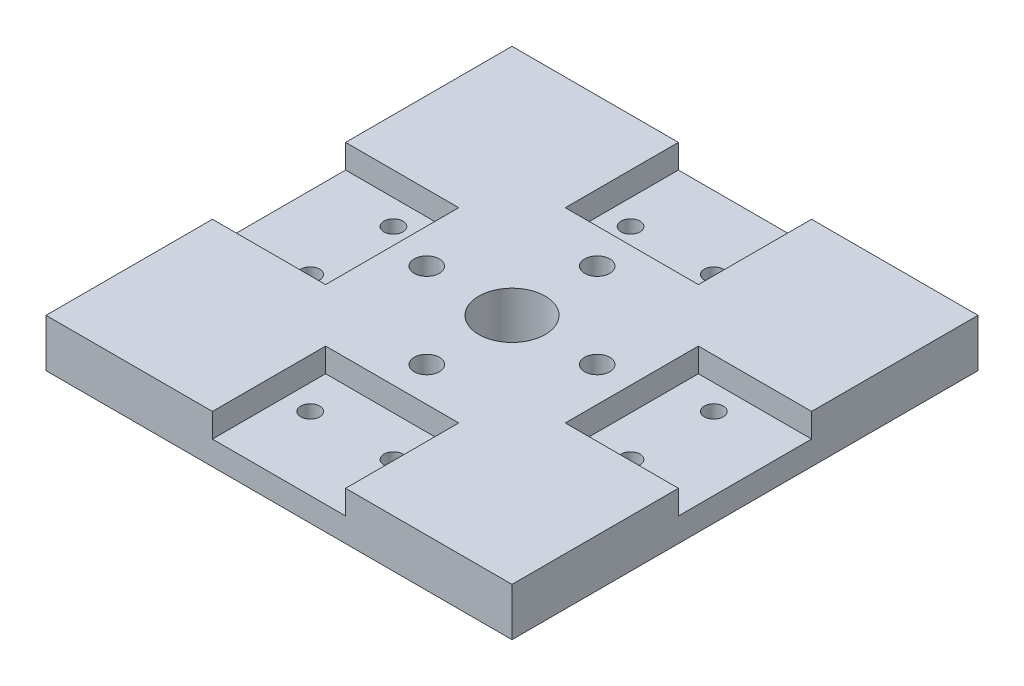
SolidWorks part; units mm, degrees
material "6061 Alloy"
ref_plane "Front Plane" through (0, 0, 0) normal (0, 0, 1) x (1, 0, 0)
ref_plane "Top Plane" through (0, 0, 0) normal (0, 1, 0) x (1, 0, 0)
ref_plane "Right Plane" through (0, 0, 0) normal (1, 0, 0) x (0, 0, -1)
sketch "Sketch1" plane through (0, 0, 0) normal (0, 1, 0) x (1, 0, 0)
  line L1 (0, 0) -> (88.9, 0)
  line L2 (0, 0) -> (0, 88.9)
  line L3 (0, 88.9) -> (88.9, 88.9)
  line L4 (88.9, 0) -> (88.9, 88.9)
  dimension "D1" = 88.9
  dimension "D2" = 88.9
extrude "Boss-Extrude1" add sketch "Sketch1" along normal blind 9.144
sketch "Sketch2" plane through (0, 9.144, 0) normal (0, 1, 0) x (1, 0, 0)
  line L0 (88.9, 88.9) -> (0, 88.9) construction
  line L1 (31.75, 88.9) -> (57.15, 88.9)
  line L2 (31.75, 88.9) -> (31.75, 67.31)
  line L3 (31.75, 67.31) -> (57.15, 67.31)
  line L4 (57.15, 88.9) -> (57.15, 67.31)
  line L5 (0, 88.9) -> (0, 0) construction
  line L6 (0, 57.15) -> (21.59, 57.15)
  line L7 (0, 57.15) -> (0, 31.75)
  line L8 (0, 31.75) -> (21.59, 31.75)
  line L9 (21.59, 57.15) -> (21.59, 31.75)
  line L10 (0, 0) -> (88.9, 0) construction
  line L11 (31.75, 0) -> (57.15, 0)
  line L12 (31.75, 0) -> (31.75, 21.59)
  line L13 (31.75, 21.59) -> (57.15, 21.59)
  line L14 (57.15, 0) -> (57.15, 21.59)
  line L15 (88.9, 0) -> (88.9, 88.9) construction
  line L16 (88.9, 57.15) -> (67.31, 57.15)
  line L17 (88.9, 57.15) -> (88.9, 31.75)
  line L18 (88.9, 31.75) -> (67.31, 31.75)
  line L19 (67.31, 57.15) -> (67.31, 31.75)
  dimension "D1" = 31.75
  dimension "D2" = 25.4
  dimension "D3" = 25.4
  dimension "D4" = 31.75
  dimension "D5" = 25.4
  dimension "D6" = 31.75
  dimension "D7" = 25.4
  dimension "D8" = 31.75
  dimension "D9" = 21.59
  dimension "D10" = 21.59
  dimension "D11" = 21.59
  dimension "D12" = 21.59
extrude "Cut-Extrude1" cut sketch "Sketch2" against normal blind 4.572
sketch "Sketch3" plane through (0, 9.144, 0) normal (0, 1, 0) x (1, 0, 0)
  line L0 (31.75, 88.9) -> (0, 88.9) construction
  line L1 (20.6375, 68.2625) -> (68.2625, 68.2625)
  line L2 (20.6375, 68.2625) -> (20.6375, 20.6375)
  line L3 (20.6375, 20.6375) -> (68.2625, 20.6375)
  line L4 (68.2625, 68.2625) -> (68.2625, 20.6375)
  line L5 (0, 31.75) -> (0, 0) construction
  line L6 (88.9, 31.75) -> (88.9, 57.15) construction
  line L7 (57.15, 88.9) -> (31.75, 88.9) construction
  line L8 (0, 57.15) -> (0, 31.75) construction
  line L9 (31.75, 0) -> (57.15, 0) construction
  circle A0 centre (28.194, 44.45) radius 2.4
  circle A1 centre (44.45, 60.706) radius 2.4
  circle A2 centre (60.706, 44.45) radius 2.4
  circle A3 centre (44.45, 28.194) radius 2.4
  point P16 (0, 0)
  dimension "D5" = 4.8
  dimension "D6" = 4.8
  dimension "D7" = 4.8
  dimension "D8" = 4.8
  dimension "D1" = 47.625
  dimension "D2" = 47.625
  dimension "D3" = 20.6375
  dimension "D4" = 20.6375
  dimension "D9" = 28.194
  dimension "D10" = 28.194
  dimension "D11" = 28.194
  dimension "D12" = 28.194
  dimension "D13" = 23.8125
  dimension "D14" = 23.8125
  dimension "D15" = 23.8125
  dimension "D16" = 23.8125
extrude "Cut-Extrude2" cut sketch "Sketch3" against normal through all contours A2 | A1 | A0 | A3
sketch "Sketch4" plane through (0, 4.572, 0) normal (0, 1, 0) x (1, 0, 0)
  line L0 (0, 57.15) -> (0, 31.75) construction
  line L1 (57.15, 88.9) -> (31.75, 88.9) construction
  line L2 (88.9, 31.75) -> (88.9, 57.15) construction
  line L3 (31.75, 0) -> (57.15, 0) construction
  line L4 (0, 31.75) -> (21.59, 31.75) construction
  line L5 (31.75, 21.59) -> (31.75, 0) construction
  line L6 (67.31, 31.75) -> (88.9, 31.75) construction
  line L7 (57.15, 67.31) -> (57.15, 88.9) construction
  circle A0 centre (75.0062, 52.3875) radius 1.8034
  circle A1 centre (75.0062, 36.5125) radius 1.8034
  circle A2 centre (52.3875, 75.0062) radius 1.8034
  circle A3 centre (36.5125, 75.0062) radius 1.8034
  circle A4 centre (13.8938, 52.3875) radius 1.8034
  circle A5 centre (13.8938, 36.5125) radius 1.8034
  circle A6 centre (36.5125, 13.8938) radius 1.8034
  circle A7 centre (52.3875, 13.8938) radius 1.8034
  dimension "D1" = 3.6068
  dimension "D2" = 3.6068
  dimension "D3" = 3.6068
  dimension "D4" = 3.6068
  dimension "D5" = 3.6068
  dimension "D6" = 3.6068
  dimension "D7" = 3.6068
  dimension "D8" = 3.6068
  dimension "D9" = 13.8938
  dimension "D10" = 13.8938
  dimension "D11" = 13.8938
  dimension "D12" = 13.8938
  dimension "D13" = 13.8938
  dimension "D14" = 13.8938
  dimension "D15" = 13.8938
  dimension "D16" = 13.8938
  dimension "D17" = 15.875
  dimension "D18" = 4.7625
  dimension "D19" = 4.7625
  dimension "D20" = 15.875
  dimension "D21" = 4.7625
  dimension "D22" = 15.875
  dimension "D23" = 4.7625
  dimension "D24" = 15.875
extrude "Cut-Extrude3" cut sketch "Sketch4" against normal through all
sketch "Sketch5" plane through (0, 9.144, 0) normal (0, 1, 0) x (1, 0, 0)
  line L0 (88.9, 88.9) -> (57.15, 88.9) construction
  line L1 (88.9, 31.75) -> (88.9, 57.15) construction
  circle A0 centre (44.45, 44.45) radius 6.35
  dimension "D1" = 12.7
  dimension "D2" = 44.45
  dimension "D3" = 44.45
extrude "Cut-Extrude4" cut sketch "Sketch5" against normal through all
equation "\"hinge_hole\"= 0.142in"
equation "\"D1@Sketch4\"=\"hinge_hole\""
equation "\"D2@Sketch4\"=\"hinge_hole\""
equation "\"D3@Sketch4\"=\"hinge_hole\""
equation "\"D4@Sketch4\"=\"hinge_hole\""
equation "\"D5@Sketch4\"=\"hinge_hole\""
equation "\"D6@Sketch4\"=\"hinge_hole\""
equation "\"D7@Sketch4\"=\"hinge_hole\""
equation "\"D8@Sketch4\"=\"hinge_hole\""
equation "\"hinge_hole_dist\"= 0.297 + 0.25"
equation "\"D9@Sketch4\"=\"hinge_hole_dist\""
equation "\"D10@Sketch4\"=\"hinge_hole_dist\""
equation "\"D11@Sketch4\"=\"hinge_hole_dist\""
equation "\"D12@Sketch4\"=\"hinge_hole_dist\""
equation "\"D13@Sketch4\"=\"hinge_hole_dist\""
equation "\"D14@Sketch4\"=\"hinge_hole_dist\""
equation "\"D15@Sketch4\"=\"hinge_hole_dist\""
equation "\"D16@Sketch4\"=\"hinge_hole_dist\""
equation "\"hinge_hole_sep\"= 0.625"
equation "\"hinge_hole_from_wall\"= ( 1 - \"hinge_hole_sep\" ) / 2"
equation "\"D17@Sketch4\"=\"hinge_hole_sep\""
equation "\"D18@Sketch4\"=\"hinge_hole_from_wall\""
equation "\"D19@Sketch4\"=\"hinge_hole_from_wall\""
equation "\"D20@Sketch4\"=\"hinge_hole_sep\""
equation "\"D21@Sketch4\"=\"hinge_hole_from_wall\""
equation "\"D22@Sketch4\"=\"hinge_hole_sep\""
equation "\"D23@Sketch4\"=\"hinge_hole_from_wall\""
equation "\"D24@Sketch4\"=\"hinge_hole_sep\""
equation "\"D9@Sketch2\"=\"hinge_hole_dist\" + (0.6-0.297)"
equation "\"D12@Sketch2\"=\"hinge_hole_dist\" + (0.6-0.297)"
equation "\"D11@Sketch2\"=\"hinge_hole_dist\" + (0.6-0.297)"
equation "\"D10@Sketch2\"=\"hinge_hole_dist\" + (0.6-0.297)"
